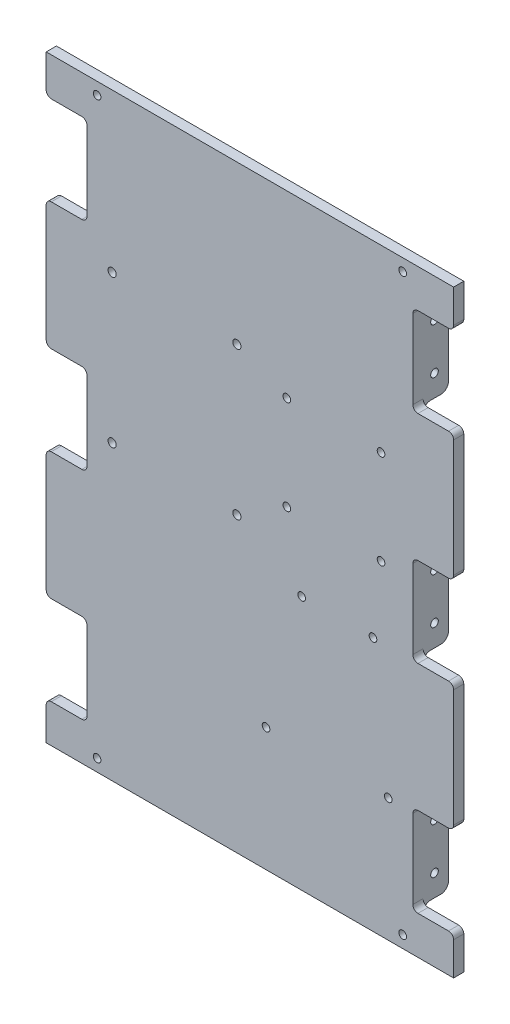
SolidWorks part; units mm, degrees
ref_plane "Front Plane" through (0, 0, 0) normal (0, 0, 1) x (1, 0, 0)
ref_plane "Top Plane" through (0, 0, 0) normal (0, 1, 0) x (1, 0, 0)
ref_plane "Right Plane" through (0, 0, 0) normal (1, 0, 0) x (0, 0, -1)
sketch "Sketch1" plane through (0, 0, 0) normal (0, 0, 1) x (1, 0, 0)
  line L0 (-64.0501, 42.5) -> (64, 42.5) construction
  line L5 (80, 25) -> (80, -25)
  line L8 (80, 25) -> (64, 25)
  line L9 (64, 60) -> (64, 25)
  line L10 (80, -60) -> (80, -75)
  line L11 (80, -60) -> (64, -60)
  line L13 (80, -25) -> (64, -25)
  line L14 (64, -60) -> (64, -25)
  line L15 (0, 75) -> (0, -75) construction
  line L25 (-64, -60) -> (-64, -25)
  line L26 (-80, -25) -> (-64, -25)
  line L27 (-80, -60) -> (-64, -60)
  line L28 (-80, -60) -> (-80, -75)
  line L29 (-64, 60) -> (-64, 25)
  line L30 (-80, 25) -> (-64, 25)
  line L32 (-80, 25) -> (-80, -25)
  line L35 (-80, -75) -> (80, -75)
  line L36 (0, 10) -> (0, 160) construction
  line L37 (-80, 160) -> (80, 160)
  line L38 (-80, 60) -> (-80, 110)
  line L39 (-80, 60) -> (-64, 60)
  line L40 (-80, 145) -> (-80, 160)
  line L41 (-80, 145) -> (-64, 145)
  line L42 (-80, 110) -> (-64, 110)
  line L43 (-64, 145) -> (-64, 110)
  line L44 (64, 145) -> (64, 110)
  line L45 (80, 110) -> (64, 110)
  line L46 (80, 145) -> (64, 145)
  line L47 (80, 145) -> (80, 160)
  line L48 (80, 60) -> (64, 60)
  line L49 (80, 60) -> (80, 110)
  point P27 (-64, 42.5)
extrude "Boss-Extrude1" add sketch "Sketch1" against normal blind 4
sketch "Sketch4" plane through (0, 0, 0) normal (0, 0, 1) x (1, 0, 0)
  line L0 (-64, -60) -> (-54, -60)
  line L5 (80, 0) -> (-80, 0) construction
  line L6 (64, 60) -> (54, 60)
  line L7 (64, 60) -> (64, 25)
  line L8 (64, 25) -> (54, 25)
  line L9 (54, 60) -> (54, 25)
  line L10 (80, -25) -> (80, 25) construction
  line L11 (-80, 25) -> (-80, -25) construction
  line L12 (54, -60) -> (54, -25)
  line L13 (64, -25) -> (54, -25)
  line L14 (64, -60) -> (64, -25)
  line L15 (64, -60) -> (54, -60)
  line L16 (0, 75) -> (0, -75) construction
  line L18 (-80, -75) -> (80, -75) construction
  line L19 (-64, -60) -> (-64, -25)
  line L20 (-64, -25) -> (-54, -25)
  line L21 (-54, -60) -> (-54, -25)
  line L22 (-54, 60) -> (-54, 25)
  line L23 (-64, 25) -> (-54, 25)
  line L24 (-64, 60) -> (-64, 25)
  line L25 (-64, 60) -> (-54, 60)
  line L26 (-80, 85) -> (80, 85) construction
  line L27 (-80, 110) -> (-80, 60) construction
  line L28 (80, 60) -> (80, 110) construction
  line L29 (-64, 110) -> (-54, 110)
  line L30 (-64, 110) -> (-64, 145)
  line L31 (-64, 145) -> (-54, 145)
  line L32 (-54, 110) -> (-54, 145)
  line L33 (54, 110) -> (54, 145)
  line L34 (64, 145) -> (54, 145)
  line L35 (64, 110) -> (64, 145)
  line L36 (64, 110) -> (54, 110)
extrude "Boss-Extrude3" add sketch "Sketch4" against normal blind 14
sketch "Sketch6" plane through (64, 0, 0) normal (1, 0, 0) x (0, 0, -1)
  line L0 (8.5, -60) -> (8.5, -25) construction
  line L1 (14, 110) -> (14, 145) construction
  line L2 (0, 60) -> (0, 110) construction
  line L3 (8.5, -42.5) -> (14, -42.5) construction
  line L4 (0, -25) -> (0, 25) construction
  line L5 (8.5, 0) -> (0, 0) construction
  line L7 (8.5, 42.5) -> (14, 42.5) construction
  line L8 (8.5, 60) -> (8.5, 25) construction
  line L9 (8.5, 85) -> (0, 85) construction
  line L11 (8.5, 110) -> (8.5, 145) construction
  line L12 (8.5, 127.5) -> (14, 127.5) construction
  line L13 (8.5, 145) -> (8.5, -60) construction
  line L16 (8.5, 42.5) -> (14, 42.5) construction
  circle A0 centre (8.5, -51.5) radius 1.5
  circle A1 centre (8.5, -33.5) radius 1.5
  circle A2 centre (8.5, 33.5) radius 1.5
  circle A3 centre (8.5, 51.5) radius 1.5
  circle A4 centre (8.5, 118.5) radius 1.5
  circle A5 centre (8.5, 136.5) radius 1.5
extrude "Cut-Extrude1" cut sketch "Sketch6" against normal up to surface (128 mm away) up to face at (-64, -42.5, -6)
fillet "Fillet2" radius 3 24 edges at (-59, -25, -14) (-59, -60, -14) (-59, 60, -14) (-59, 25, -14) (-59, 145, -14) (-59, 110, -14) (59, 145, -14) (59, 110, -14) (59, 25, -14) (59, 60, -14) (59, -25, -14) (59, -60, -14) (59, 145, -4) (59, 110, -4) (59, 60, -4) (59, 25, -4) (59, -25, -4) (59, -60, -4) (-59, -25, -4) (-59, -60, -4) (-59, 25, -4) (-59, 60, -4) (-59, 110, -4) (-59, 145, -4)
fillet "Fillet3" radius 2 24 edges at (80, -60, -2) (64, -60, -2) (80, -25, -2) (64, -25, -2) (80, 25, -2) (64, 25, -2) (64, 60, -2) (80, 60, -2) (80, 110, -2) (64, 110, -2) (64, 145, -2) (80, 145, -2) (-80, 145, -2) (-64, 145, -2) (-64, 110, -2) (-80, 110, -2) (-80, 60, -2) (-64, 60, -2) (-64, 25, -2) (-80, 25, -2) (-80, -25, -2) (-64, -25, -2) (-80, -60, -2) (-64, -60, -2)
sketch "Sketch7" plane through (0, 0, -4) normal (0, 0, -1) x (-1, 0, 0)
  line L0 (2.5, 125.5) -> (32.5, 125.5)
  line L8 (32.5, 40.5) -> (2.5, 40.5)
  line L9 (32.5, -40.5) -> (32.5, 40.5)
  line L10 (2.5, -40.5) -> (32.5, -40.5)
  line L11 (2.5, 40.5) -> (2.5, -40.5)
  line L13 (36.5, 125.5) -> (64, 125.5)
  line L16 (2.5, 44.5) -> (32.5, 44.5)
  line L17 (32.5, 44.5) -> (32.5, 125.5)
  line L19 (2.5, 125.5) -> (2.5, 44.5)
  line L24 (-32.5, -40.5) -> (-2.5, -40.5)
  line L25 (-32.5, 40.5) -> (-32.5, -40.5)
  line L26 (-2.5, 40.5) -> (-32.5, 40.5)
  line L27 (-2.5, -40.5) -> (-2.5, 40.5)
  line L32 (-2.5, 125.5) -> (-32.5, 125.5)
  line L33 (-32.5, 125.5) -> (-32.5, 44.5)
  line L34 (-32.5, 44.5) -> (-2.5, 44.5)
  line L35 (-2.5, 44.5) -> (-2.5, 125.5)
  line L76 (0, 129.5) -> (-64, 129.5)
  line L77 (-64, 129.5) -> (-64, 125.5)
  line L78 (-64, 125.5) -> (-36.5, 125.5)
  line L79 (-36.5, 125.5) -> (-36.5, 44.5)
  line L80 (-36.5, 44.5) -> (-64, 44.5)
  line L81 (-64, 44.5) -> (-64, 40.5)
  line L82 (-64, 40.5) -> (-36.5, 40.5)
  line L83 (-36.5, 40.5) -> (-36.5, -40.5)
  line L84 (-36.5, -40.5) -> (-64, -40.5)
  line L85 (-64, -40.5) -> (-64, -44.5)
  line L86 (-64, -44.5) -> (0, -44.5)
  line L87 (0, -44.5) -> (64, -44.5)
  line L88 (64, -44.5) -> (64, -40.5)
  line L89 (64, -40.5) -> (36.5, -40.5)
  line L90 (36.5, -40.5) -> (36.5, 40.5)
  line L91 (36.5, 40.5) -> (64, 40.5)
  line L92 (64, 40.5) -> (64, 44.5)
  line L93 (64, 44.5) -> (36.5, 44.5)
  line L94 (36.5, 44.5) -> (36.5, 125.5)
  line L96 (64, 125.5) -> (64, 129.5)
  line L97 (64, 129.5) -> (0, 129.5)
  dimension "D1" = 4
  dimension "D2" = 4
  dimension "D3" = 4
  dimension "D4" = 4
  dimension "D5" = 30
  dimension "D6" = 30
  dimension "D7" = 30
  dimension "D8" = 30
extrude "Boss-Extrude4" add sketch "Sketch7" along normal blind 7
fillet "Fillet4" radius 4 34 edges at (54, -44.5, -7.5) (54, -40.5, -7.5) (36.5, -40.5, -7.5) (32.5, -40.5, -7.5) (-2.5, -40.5, -7.5) (2.5, -40.5, -7.5) (-32.5, -40.5, -7.5) (-36.5, -40.5, -7.5) (-54, -44.5, -7.5) (-54, -40.5, -7.5) (-54, 44.5, -7.5) (-36.5, 44.5, -7.5) (-36.5, 40.5, -7.5) (-32.5, 40.5, -7.5) (-32.5, 44.5, -7.5) (54, 40.5, -7.5) (54, 44.5, -7.5) (-2.5, 44.5, -7.5) (2.5, 40.5, -7.5) (2.5, 44.5, -7.5) (36.5, 44.5, -7.5) (36.5, 40.5, -7.5) (32.5, 40.5, -7.5) (32.5, 44.5, -7.5) (54, 129.5, -7.5) (54, 125.5, -7.5) (36.5, 125.5, -7.5) (32.5, 125.5, -7.5) (2.5, 125.5, -7.5) (-2.5, 125.5, -7.5) (-32.5, 125.5, -7.5) (-36.5, 125.5, -7.5) (-54, 125.5, -7.5) (-54, 129.5, -7.5)
sketch "Sketch8" plane through (0, 0, 0) normal (0, 0, 1) x (1, 0, 0)
  circle A0 centre (-60, 155.25) radius 1.5
  circle A1 centre (60, 155.25) radius 1.5
  circle A2 centre (-60, -70.25) radius 1.5
  circle A3 centre (60, -70.25) radius 1.5
extrude "Cut-Extrude2" cut sketch "Sketch8" against normal through all
sketch "Sketch9" plane through (0, 0, 0) normal (0, 0, 1) x (1, 0, 0)
  circle A0 centre (51.5, 89.5) radius 1.5
  circle A1 centre (51.5, 52.5) radius 1.5
  circle A2 centre (14.5, 52.5) radius 1.5
  circle A3 centre (14.5, 89.5) radius 1.5
  circle A4 centre (-5.1095, 97.9735) radius 1.6
  circle A5 centre (-54.1095, 97.9735) radius 1.6
  circle A6 centre (-54.1095, 39.9735) radius 1.6
  circle A7 centre (-5.1095, 39.9735) radius 1.6
  circle A8 centre (48.3388, 24.9461) radius 1.5
  circle A9 centre (20.3388, 24.9461) radius 1.5
  circle A10 centre (6.3388, -26.5539) radius 1.5
  circle A11 centre (54.3388, -26.5539) radius 1.5
extrude "Cut-Extrude3" cut sketch "Sketch9" against normal through all
sketch "Sketch10" plane through (0, 0, -4) normal (0, 0, -1) x (-1, 0, 0)
  line L1 (2.2228, 39.9735) -> (3.6661, 37.4735)
  line L2 (3.6661, 37.4735) -> (6.5529, 37.4735)
  line L3 (6.5529, 37.4735) -> (7.9963, 39.9735)
  line L4 (7.9963, 39.9735) -> (6.5529, 42.4735)
  line L5 (6.5529, 42.4735) -> (3.6661, 42.4735)
  line L6 (3.6661, 42.4735) -> (2.2228, 39.9735)
  line L7 (56.9963, 39.9735) -> (55.5529, 42.4735)
  line L8 (55.5529, 42.4735) -> (52.6661, 42.4735)
  line L9 (52.6661, 42.4735) -> (51.2228, 39.9735)
  line L10 (51.2228, 39.9735) -> (52.6661, 37.4735)
  line L11 (52.6661, 37.4735) -> (55.5529, 37.4735)
  line L12 (55.5529, 37.4735) -> (56.9963, 39.9735)
  line L13 (-54.3388, -23.6672) -> (-56.8388, -25.1105)
  line L14 (-56.8388, -25.1105) -> (-56.8388, -27.9973)
  line L15 (-56.8388, -27.9973) -> (-54.3388, -29.4407)
  line L16 (-54.3388, -29.4407) -> (-51.8388, -27.9973)
  line L17 (-51.8388, -27.9973) -> (-51.8388, -25.1105)
  line L18 (-51.8388, -25.1105) -> (-54.3388, -23.6672)
  circle A0 centre (5.1095, 39.9735) radius 2.5 construction
  circle A1 centre (54.1095, 39.9735) radius 2.5 construction
  circle A2 centre (-54.3388, -26.5539) radius 2.5 construction
extrude "Cut-Extrude4" cut sketch "Sketch10" along normal up to surface (10 mm away) up to face at (-57.6183, 41.6578, -14)
